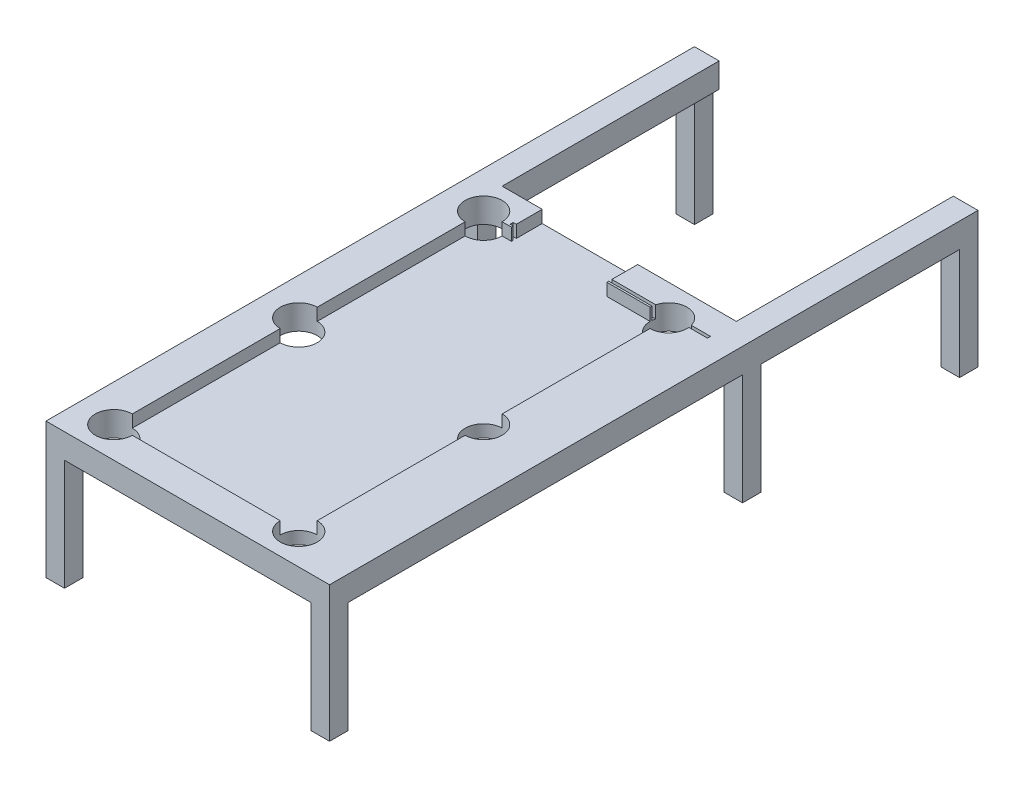
SolidWorks part; units mm, degrees
ref_plane "Front Plane" through (0, 0, 0) normal (0, 0, 1) x (1, 0, 0)
ref_plane "Top Plane" through (0, 0, 0) normal (0, 1, 0) x (1, 0, 0)
ref_plane "Right Plane" through (0, 0, 0) normal (1, 0, 0) x (0, 0, -1)
sketch "Sketch2" plane through (0, 0, 0) normal (0, 1, 0) x (1, 0, 0)
  line L1 (0, 0) -> (460, 0)
  line L2 (0, 0) -> (0, 700)
  line L3 (0, 700) -> (460, 700)
  line L4 (460, 0) -> (460, 700)
  line L5 (60, 50) -> (360, 50)
  line L6 (60, 50) -> (60, 650)
  line L7 (60, 650) -> (360, 650)
  line L8 (360, 50) -> (360, 650)
  dimension "D1" = 700
  dimension "D2" = 460
  dimension "D3" = 600
  dimension "D4" = 300
  dimension "D5" = 60
  dimension "D6" = 50
extrude "Boss-Extrude1" add sketch "Sketch2" along normal blind 20
ref_plane "Plane1" through (0, 0, -700) normal (0, 0, -1) x (-1, 0, 0)
sketch "Sketch10" plane through (0, 0, 0) normal (0, -1, 0) x (1, 0, 0)
  line L1 (0, 0) -> (460, 0)
  line L2 (0, 0) -> (0, -700)
  line L3 (0, -700) -> (460, -700)
  line L4 (460, 0) -> (460, -700)
extrude "Boss-Extrude6" add sketch "Sketch10" along normal blind 20
sketch "Sketch11" plane through (0, -20, 0) normal (0, -1, 0) x (1, 0, 0)
  line L1 (0, 0) -> (30, 0)
  line L2 (0, 0) -> (0, -30)
  line L3 (0, -30) -> (30, -30)
  line L4 (30, 0) -> (30, -30)
  line L5 (460, 0) -> (430, 0)
  line L6 (460, 0) -> (460, -30)
  line L7 (460, -30) -> (430, -30)
  line L8 (430, 0) -> (430, -30)
  line L9 (0, -700) -> (30, -700)
  line L10 (0, -700) -> (0, -670)
  line L11 (0, -670) -> (30, -670)
  line L12 (30, -700) -> (30, -670)
  line L13 (460, -700) -> (430, -700)
  line L14 (460, -700) -> (460, -670)
  line L15 (460, -670) -> (430, -670)
  line L16 (430, -700) -> (430, -670)
  dimension "D1" = 30
extrude "Boss-Extrude7" add sketch "Sketch11" along normal blind 180
sketch "Sketch14" plane through (0, 20, 0) normal (0, 1, 0) x (1, 0, 0)
  line L0 (22, 700) -> (-22, 700) construction
  line L1 (0, 700) -> (40, 700)
  line L2 (0, 700) -> (0, 1052)
  line L3 (0, 1052) -> (40, 1052)
  line L4 (40, 700) -> (40, 1052)
  line L5 (0, 700) -> (0, 0) construction
  line L6 (460, 0) -> (460, 700) construction
  line L7 (460, 700) -> (420, 700)
  line L8 (460, 700) -> (460, 1052)
  line L9 (460, 1052) -> (420, 1052)
  line L10 (420, 700) -> (420, 1052)
  line L11 (330, 1052) -> (390, 1052) construction
  dimension "D3" = 40
  dimension "D4" = 40
extrude "Boss-Extrude8" add sketch "Sketch14" against normal blind 40
sketch "Sketch15" plane through (0, -20, 0) normal (0, -1, 0) x (1, 0, 0)
  line L1 (460, -1052) -> (430, -1052)
  line L2 (460, -1052) -> (460, -1022)
  line L3 (460, -1022) -> (430, -1022)
  line L4 (430, -1052) -> (430, -1022)
  line L6 (0, -1052) -> (30, -1052)
  line L7 (0, -1052) -> (0, -1022)
  line L8 (0, -1022) -> (30, -1022)
  line L9 (30, -1052) -> (30, -1022)
  dimension "D1" = 30
  dimension "D2" = 30
  dimension "D3" = 30
  dimension "D4" = 30
extrude "Boss-Extrude9" add sketch "Sketch15" along normal blind 180
sketch "Sketch17" plane through (0, 20, 0) normal (0, 1, 0) x (1, 0, 0)
  line L0 (60, 650) -> (60, 50) construction
  line L1 (360, 50) -> (360, 650) construction
  circle A0 centre (60, 650) radius 30
  circle A1 centre (60, 350) radius 30
  circle A2 centre (60, 50) radius 30
  circle A3 centre (360, 50) radius 30
  circle A4 centre (360, 350) radius 30
  circle A5 centre (360, 650) radius 30
  line M15 (60, 50) -> (60, 650)
  line M16 (60, 650) -> (360, 650)
  line M17 (360, 650) -> (360, 50)
  line M18 (360, 50) -> (60, 50)
  dimension "D1" = 60
extrude "Cut-Extrude1" cut sketch "Sketch17" against normal blind 60 contours A5 M17 M16 | A4 M17 | A3 M18 M17 | A1 M15 | A1 M15 | A2 M15 M18 | A2 M18 M15 | A3 M17 M18 | A5 M16 M17 | A4 M17 | A0 region at (347.2676, 20, -637.2676) region at (364.2441, 20, -654.2441) region at (47.2676, 20, -350) region at (72.7324, 20, -350) region at (347.2676, 20, -350) region at (372.7324, 20, -350) region at (55.7559, 20, -45.7559) region at (72.7324, 20, -62.7324) region at (347.2676, 20, -62.7324) region at (364.2441, 20, -45.7559)
sketch "Sketch18" plane through (0, 20, 0) normal (0, 1, 0) x (1, 0, 0)
  line L9 (330, 650) -> (90, 650) construction
  line L10 (420, 700) -> (40, 700) construction
  line L11 (182.5, 700) -> (260, 700)
  line L12 (260, 700) -> (260, 650)
  line L13 (330, 650) -> (90, 650) construction
  line L14 (210, 650) -> (260, 650)
  line L15 (182.5, 700) -> (105, 700)
  line L16 (105, 700) -> (105, 650)
  line L17 (105, 650) -> (210, 650)
  dimension "D1" = 77.5
  dimension "D2" = 77.5
  dimension "D3" = 70
extrude "Cut-Extrude2" cut sketch "Sketch18" against normal blind 20
sketch "Sketch19" plane through (105, 0, 0) normal (1, 0, 0) x (0, 0, -1)
  line L0 (650, 0) -> (652.5, 0) construction
  line L1 (700, 0) -> (650, 0) construction
  line L2 (652.5, 0) -> (652.5, 2.5) construction
  line L4 (652.5, 2.5) -> (650, 2.5)
  line L5 (652.5, 2.5) -> (652.5, 0)
  line L6 (652.5, 0) -> (650, 0)
  line L7 (650, 2.5) -> (650, 0)
  point P8 (652.5, 2.5)
  dimension "D1" = 2.5
  dimension "D2" = 2.5
sketch "Sketch20" plane through (0, 20, 0) normal (0, 1, 0) x (1, 0, 0)
  line L0 (105, 650) -> (90, 650) construction
  line L1 (100, 658) -> (420, 658)
  line L2 (100, 658) -> (100, 653)
  line L3 (100, 653) -> (420, 653)
  line L4 (420, 658) -> (420, 653)
  dimension "D1" = 320
  dimension "D2" = 5
  dimension "D3" = 3
  dimension "D4" = 5
extrude "Cut-Extrude3" cut sketch "Sketch20" against normal blind 20
